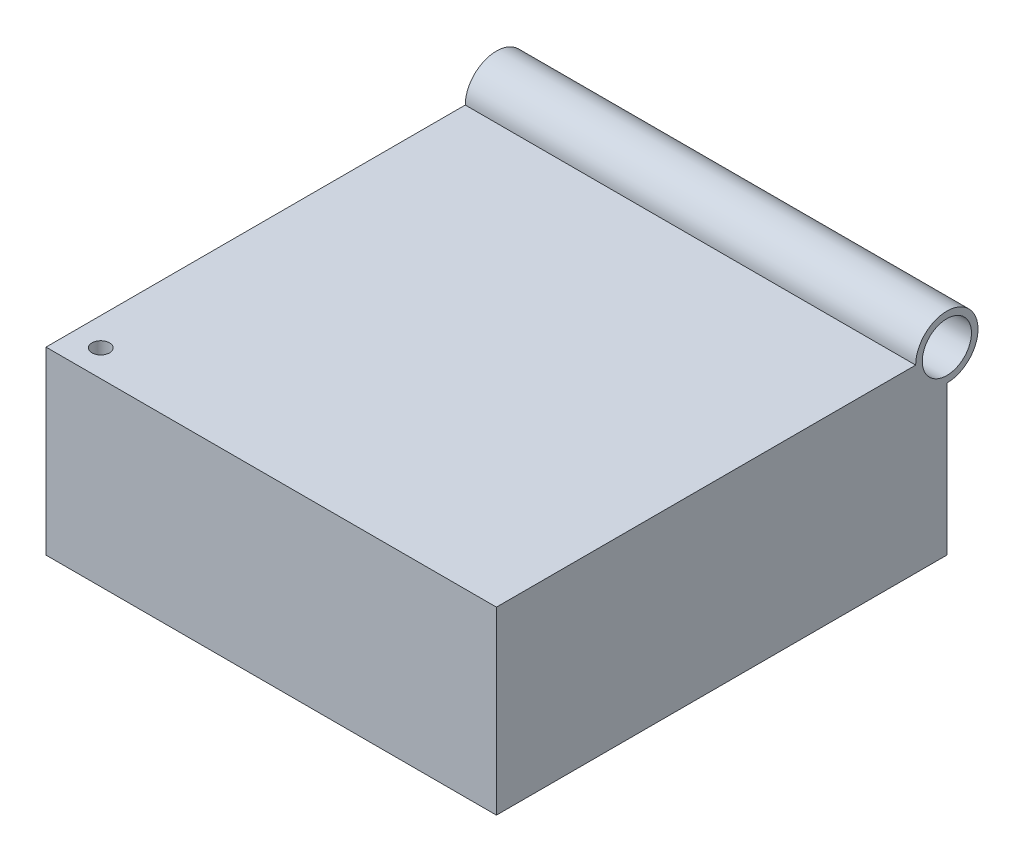
SolidWorks part; units mm, degrees
ref_plane "Front Plane" through (0, 0, 0) normal (0, 0, 1) x (1, 0, 0)
ref_plane "Top Plane" through (0, 0, 0) normal (0, 1, 0) x (1, 0, 0)
ref_plane "Right Plane" through (0, 0, 0) normal (1, 0, 0) x (0, 0, -1)
sketch "Sketch1" plane through (0, 0, 0) normal (0, 1, 0) x (1, 0, 0)
  line L1 (-65, 65) -> (65, 65)
  line L2 (-65, 65) -> (-65, -65)
  line L3 (-65, -65) -> (65, -65)
  line L4 (65, 65) -> (65, -65)
  line L5 (-65, 65) -> (65, -65) construction
  line L6 (-65, -65) -> (65, 65) construction
  point P0 (0, 0)
  dimension "D1" = 130
  dimension "D2" = 130
extrude "Boss-Extrude1" add sketch "Sketch1" along normal blind 52
sketch "Sketch2" plane through (0, 52, 0) normal (0, 1, 0) x (1, 0, 0)
  circle A0 centre (-56.9079, -57.2901) radius 2.5272
extrude "Cut-Extrude1" cut sketch "Sketch2" against normal blind 10
sketch "Sketch3" plane through (65, 0, 0) normal (1, 0, 0) x (0, 0, -1)
  circle A0 centre (65, 52) radius 9
  dimension "D1" = 18
extrude "Boss-Extrude2" add sketch "Sketch3" against normal up to surface (130 mm away) up to face at (-65, 26, 0)
sketch "Sketch4" plane through (65, 0, 0) normal (1, 0, 0) x (0, 0, -1)
  circle A0 centre (65, 52) radius 7.1
  dimension "D1" = 14.2
extrude "Cut-Extrude2" cut sketch "Sketch4" against normal up to surface (130 mm away) up to face at (-65, 31.5728, -13.3728)
